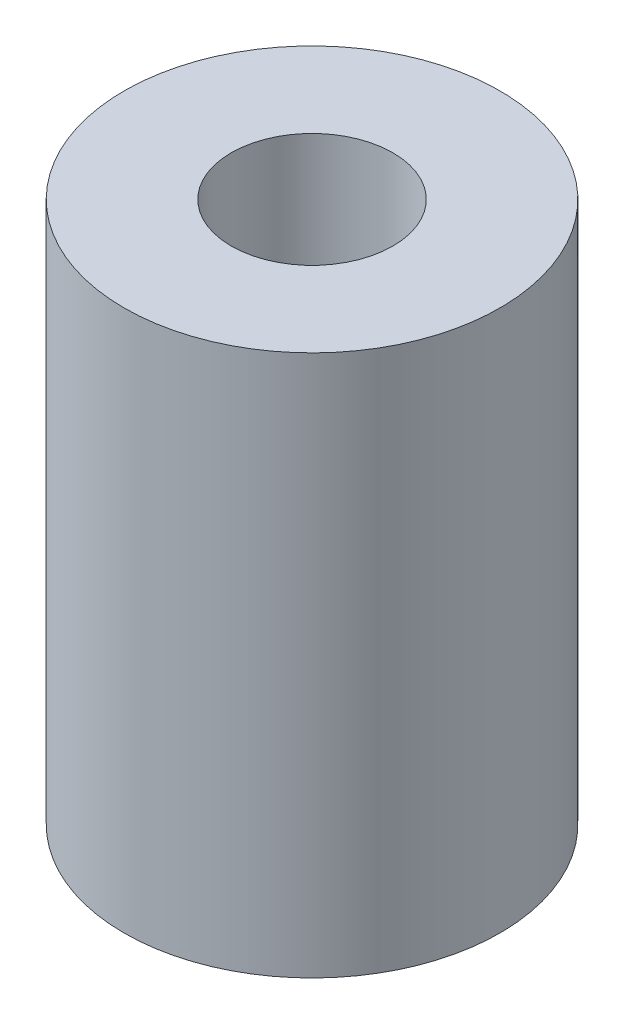
SolidWorks part; units mm, degrees
ref_plane "Front Plane" through (0, 0, 0) normal (0, 0, 1) x (1, 0, 0)
ref_plane "Top Plane" through (0, 0, 0) normal (0, 1, 0) x (1, 0, 0)
ref_plane "Right Plane" through (0, 0, 0) normal (1, 0, 0) x (0, 0, -1)
sketch "Sketch1" plane through (0, 0, 0) normal (0, 1, 0) x (1, 0, 0)
  circle A0 centre (0, 0) radius 5
  circle A1 centre (0, 0) radius 2.15
  dimension "D1" = 10
  dimension "D2" = 4.3
extrude "Boss-Extrude1" add sketch "Sketch1" along normal blind 14.4
